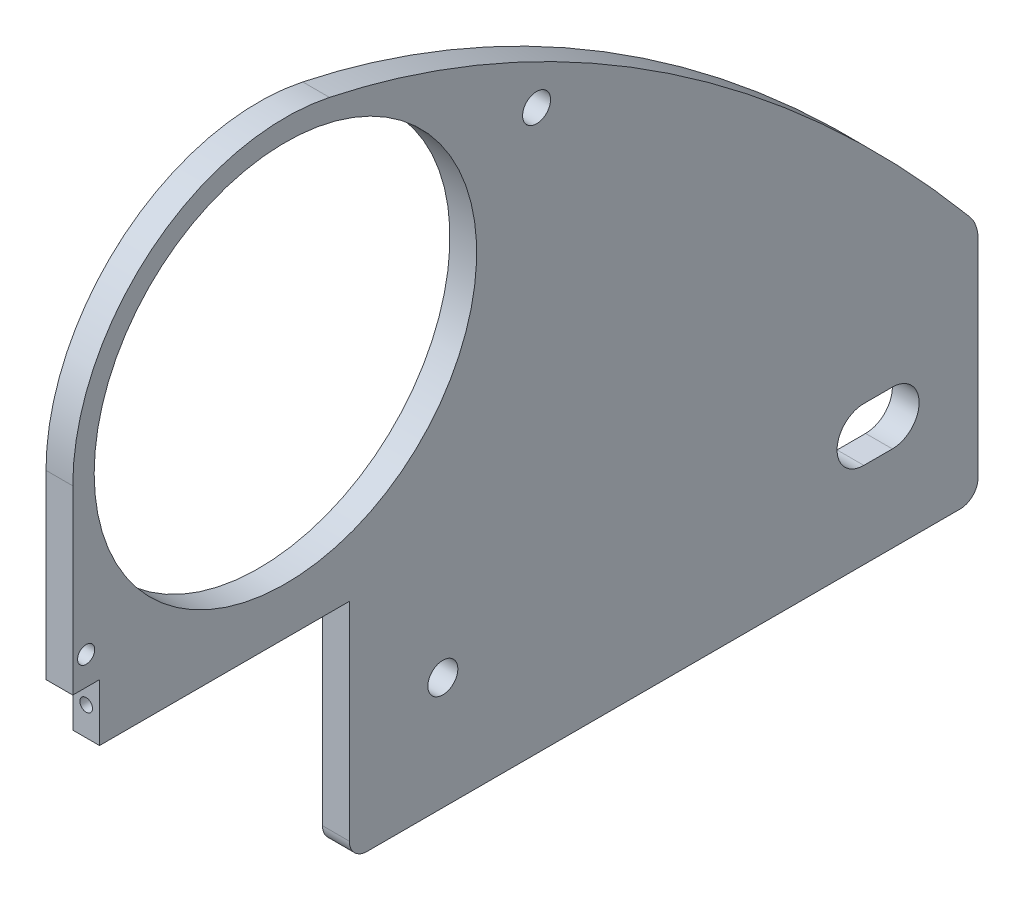
SolidWorks part; units mm, degrees
ref_plane "Front Plane" through (0, 0, 0) normal (0, 0, 1) x (1, 0, 0)
ref_plane "Top Plane" through (0, 0, 0) normal (0, 1, 0) x (1, 0, 0)
ref_plane "Right Plane" through (0, 0, 0) normal (1, 0, 0) x (0, 0, -1)
sketch "Sketch1" plane through (0, 0, 0) normal (1, 0, 0) x (0, 0, -1)
  line L0 (-28.1703, 0) -> (77.3828, 0)
  line L1 (80.5578, 3.175) -> (80.5578, 40.132)
  line L2 (-80.5578, 82.55) -> (-80.5578, 50.292)
  line L4 (-75.7953, 50.292) -> (-75.7953, 40.132)
  line L5 (65.3178, 20.066) -> (60.2378, 20.066) construction
  line L6 (65.3178, 15.3035) -> (60.2378, 15.3035)
  line L7 (-75.7953, 40.132) -> (-31.3453, 40.132)
  line L10 (-31.3453, 40.132) -> (-31.3453, 3.175)
  line L11 (-80.5578, 50.292) -> (-75.7953, 50.292)
  line L12 (65.3178, 24.8285) -> (60.2378, 24.8285)
  arc A0 (65.3178, 15.3035) -> (65.3178, 24.8285) centre (65.3178, 20.066) ccw
  circle A1 centre (-42.7078, 82.55) radius 31.5 construction
  circle A2 centre (65.3178, 20.066) radius 76.2 construction
  circle A3 centre (-78.1765, 55.372) radius 1.524
  arc A4 (60.2378, 24.8285) -> (60.2378, 15.3035) centre (60.2378, 20.066) ccw
  arc A5 (-34.8673, 119.579) -> (-80.5578, 82.55) centre (-42.7078, 82.55) ccw
  arc A6 (-28.1703, 0) -> (-31.3453, 3.175) centre (-28.1703, 3.175) cw
  arc A7 (77.3828, 0) -> (80.5578, 3.175) centre (77.3828, 3.175) ccw
  arc A8 (80.5578, 40.132) -> (79.0734, 44.2123) centre (74.2078, 40.132) ccw
  circle A9 centre (1.9922, 99.5669) radius 2.4892
  circle A10 centre (1.9922, 99.5669) radius 6.35 construction
  circle A11 centre (-14.6922, 20.066) radius 2.667
  circle A16 centre (-42.7078, 82.55) radius 34.04
  spline S0 degree 3 poles (-34.8673, 119.579) (-0.0583, 112.2086) (41.2638, 89.2986) (79.0734, 44.2123) knots 0 0 0 0 1 1 1 1
  spline S1 degree 3 poles (79.0888, 44.1938) (50.6675, 78.3472) (10.808, 109.6876) (-34.6964, 119.5424) knots 0 0 0 0 1 1 1 1 construction
  point P13 (62.7778, 20.066)
  point P28 (80.5578, 40.132)
  dimension "D4" = 9.525
  dimension "D7" = 4.7625
  dimension "D8" = 63
  dimension "D9" = 6.35
  dimension "D12" = 3.175
  dimension "D13" = 6.35
  dimension "D14" = 2.54
  dimension "D15" = 152.4
  dimension "D18" = 5.334
  dimension "D19" = 5.08
  dimension "D20" = 82.55
  dimension "D17" = 3.048
  dimension "D24" = 4.9784
  dimension "D2" = 40.132
  dimension "D3" = 20.066
  dimension "D5" = 15.24
  dimension "D6" = 44.45
  dimension "D10" = 161.1156
  dimension "D11" = 95.25
  dimension "D21" = 5.08
  dimension "D22" = 10.16
  dimension "D16" = 2.3813
extrude "Boss-Extrude1" add sketch "Sketch1" along normal blind 4.7625
sketch "Sketch2" plane through (0, 0, 75.7953) normal (0, 0, 1) x (1, 0, 0)
  line L0 (0, 50.292) -> (0, 40.132) construction
  line L1 (4.7625, 40.132) -> (0, 40.132) construction
  circle A0 centre (2.3813, 45.212) radius 1.1303
  point P4 (0, 45.212)
  point P7 (2.3813, 40.132)
  dimension "D1" = 2.2606
extrude "Cut-Extrude1" cut sketch "Sketch2" against normal blind 6.35
